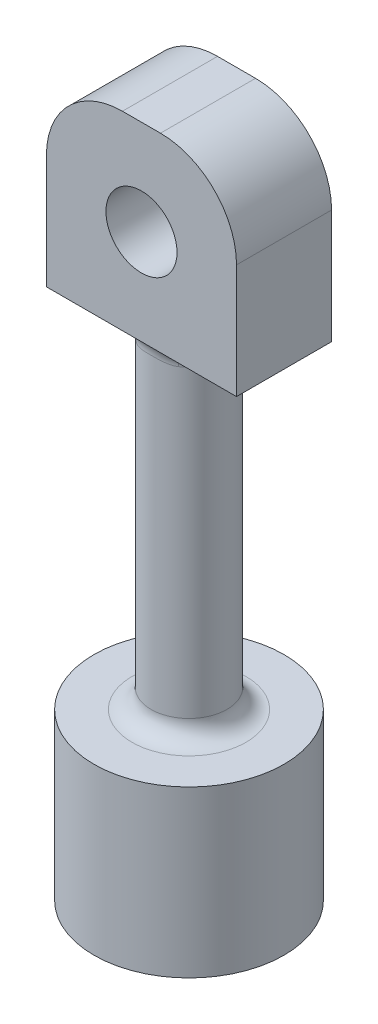
SolidWorks part; units mm, degrees
material "Plain Carbon Steel"
ref_plane "Front Plane" through (0, 0, 0) normal (0, 0, 1) x (1, 0, 0)
ref_plane "Top Plane" through (0, 0, 0) normal (0, 1, 0) x (1, 0, 0)
ref_plane "Right Plane" through (0, 0, 0) normal (1, 0, 0) x (0, 0, -1)
sketch "Sketch1" plane through (0, 0, 0) normal (0, 0, 1) x (1, 0, 0)
  line L0 (0, -55) -> (0, 55) construction
  line L1 (-6.35, 37.1853) -> (6.35, 37.1853)
  line L2 (-6.35, 37.1853) -> (-6.35, 49.8853)
  line L3 (-6.35, 49.8853) -> (6.35, 49.8853)
  line L4 (6.35, 37.1853) -> (6.35, 49.8853)
  line L5 (-6.35, 37.1853) -> (6.35, 49.8853) construction
  line L6 (-6.35, 49.8853) -> (6.35, 37.1853) construction
  point P0 (0, 43.5353)
  dimension "D1" = 12.7
  dimension "D2" = 12.7
extrude "Boss-Extrude1" add sketch "Sketch1" along normal mid plane 6.35
sketch "Sketch3" plane through (0, 37.1853, 0) normal (0, -1, 0) x (1, 0, 0)
  circle A0 centre (0, 0) radius 2.54
  dimension "D1" = 5.08
extrude "Boss-Extrude2" add sketch "Sketch3" along normal blind 22.86
sketch "Sketch4" plane through (0, 0, 0) normal (0, 0, 1) x (1, 0, 0)
  line L1 (0, 14.3253) -> (6.35, 14.3253)
  line L3 (0, 3.2763) -> (6.35, 3.2763)
  line L4 (6.35, 14.3253) -> (6.35, 3.2763)
  line L6 (0, 82.785) -> (0, -56.0219) construction
  line L8 (0, 14.3253) -> (0, 3.2763)
  dimension "D1" = 11.049
revolve "Revolve1" add sketch "Sketch4" angle 360 about L6
fillet "Fillet1" radius 1.27 2 edges at (0, 37.1853, -2.54) (0, 14.3253, -2.54)
sketch "Sketch5" plane through (0, 0, 3.175) normal (0, 0, 1) x (1, 0, 0)
  line L0 (0, 72.2335) -> (0, 31.2588) construction
  line L1 (0, -3.4925) -> (0, 3.4925) construction
  line L2 (-9.4574, 43.5353) -> (9.1985, 43.5353) construction
  line L3 (6.35, 49.8853) -> (-6.35, 49.8853) construction
  line L4 (2.1061, 37.1853) -> (6.35, 37.1853) construction
  line L5 (-6.35, 49.8853) -> (-6.35, 37.1853) construction
  line L6 (6.35, 37.1853) -> (6.35, 49.8853) construction
  circle A0 centre (0, 43.5353) radius 2.3749
  point P15 (0, 43.5353)
  dimension "D1" = 4.7498
extrude "Cut-Extrude1" cut sketch "Sketch5" against normal through all
fillet "Fillet2" radius 5.08 2 edges at (-6.35, 49.8853, 0) (6.35, 49.8853, 0)
